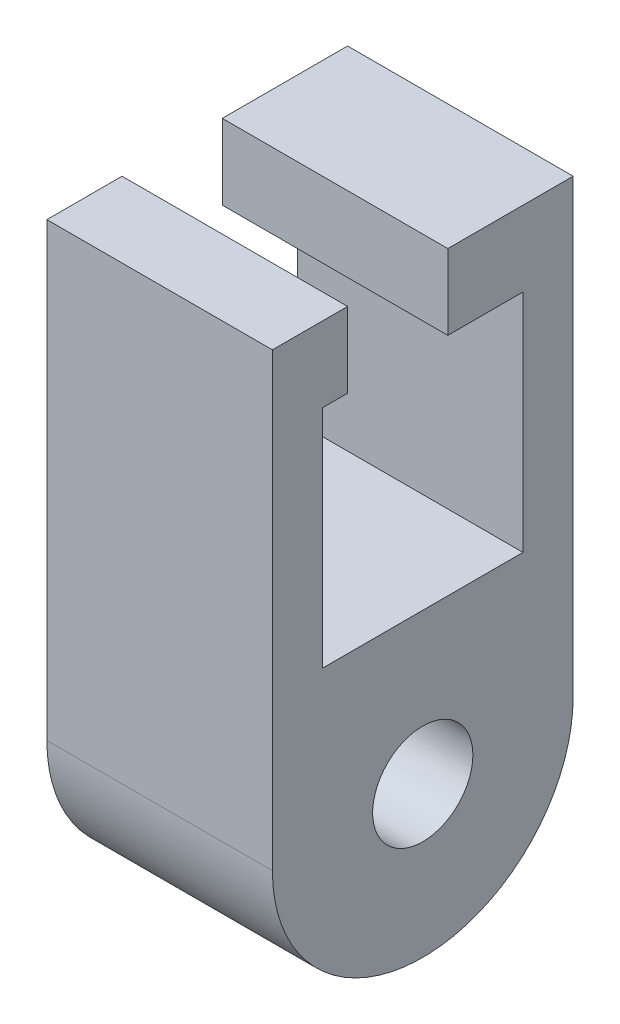
SolidWorks part; units mm, degrees
ref_plane "Front Plane" through (0, 0, 0) normal (1, 0, 0) x (0, 1, 0)
ref_plane "Top Plane" through (0, 0, 0) normal (0, 0, 1) x (0, 1, 0)
ref_plane "Right Plane" through (0, 0, 0) normal (0, 1, 0) x (-1, 0, 0)
sketch "Sketch1" plane through (0, 0, 0) normal (1, 0, 0) x (0, 1, 0)
  line L0 (0, 150) -> (450, 150)
  line L1 (450, 150) -> (450, 75)
  line L2 (450, 75) -> (375, 75)
  line L3 (375, 75) -> (375, 100)
  line L4 (375, 100) -> (150, 100)
  line L5 (150, 100) -> (150, -100)
  line L6 (150, -100) -> (375, -100)
  line L7 (375, -100) -> (375, -25)
  line L8 (375, -25) -> (450, -25)
  line L9 (450, -25) -> (450, -150)
  line L10 (450, -150) -> (0, -150)
  arc A0 (0, 150) -> (0, -150) centre (0, 0) ccw
  circle A1 centre (0, 0) radius 50
  point P15 (0, -150)
  point P16 (0, -150)
  point P17 (0, -150)
  dimension "D1" = 100
  dimension "D2" = 150
  dimension "D3" = 75
  dimension "D4" = 150
  dimension "D5" = 375
  dimension "D6" = 450
  dimension "D7" = 50
  dimension "D8" = 50
  dimension "D9" = 125
  dimension "D10" = 300
extrude "Boss-Extrude1" add sketch "Sketch1" along normal blind 112.5
mirror "Mirror1" about plane through (0, 0, 0) normal (1, 0, 0) of bodies 101
sketch "Sketch2" plane through (0, 0, 150) normal (0, 0, 1) x (1, 0, 0)
  line L0 (37.5, -150) -> (37.5, 150)
  line L1 (-112.5, -150) -> (112.5, -150) construction
  line L2 (37.5, 150) -> (112.5, 150)
  line L3 (112.5, 450) -> (112.5, 0) construction
  line L4 (12.5, 450) -> (12.5, 375)
  line L5 (112.5, 450) -> (-112.5, 450) construction
  line L6 (12.5, 375) -> (112.5, 375)
  line L9 (37.5, -150) -> (112.5, -150)
  line L10 (112.5, -150) -> (112.5, 150)
  line L11 (12.5, 450) -> (112.5, 450)
  line L12 (112.5, 450) -> (112.5, 375)
  line L13 (37.5, -150) -> (-37.5, -150)
  line L14 (-112.5, -150) -> (112.5, -150) construction
  line L15 (-37.5, -150) -> (-112.5, -150)
  line L16 (-112.5, -150) -> (-112.5, 150)
  line L17 (-112.5, 450) -> (-112.5, 0) construction
  line L18 (-112.5, 150) -> (-37.5, 150)
  line L19 (-37.5, 150) -> (-37.5, -150)
  line L20 (-12.5, 375) -> (-112.5, 375)
  line L21 (-112.5, 375) -> (-112.5, 450)
  line L22 (-112.5, 450) -> (-12.5, 450)
  line L23 (112.5, 450) -> (-112.5, 450) construction
  line L24 (-12.5, 450) -> (-12.5, 375)
  line L25 (112.5, 0) -> (-112.5, 0) construction
  point P27 (0, 0)
  dimension "D1" = 100
  dimension "D2" = 125
  dimension "D3" = 300
  dimension "D4" = 150
  dimension "D5" = 75
  dimension "D6" = 375
